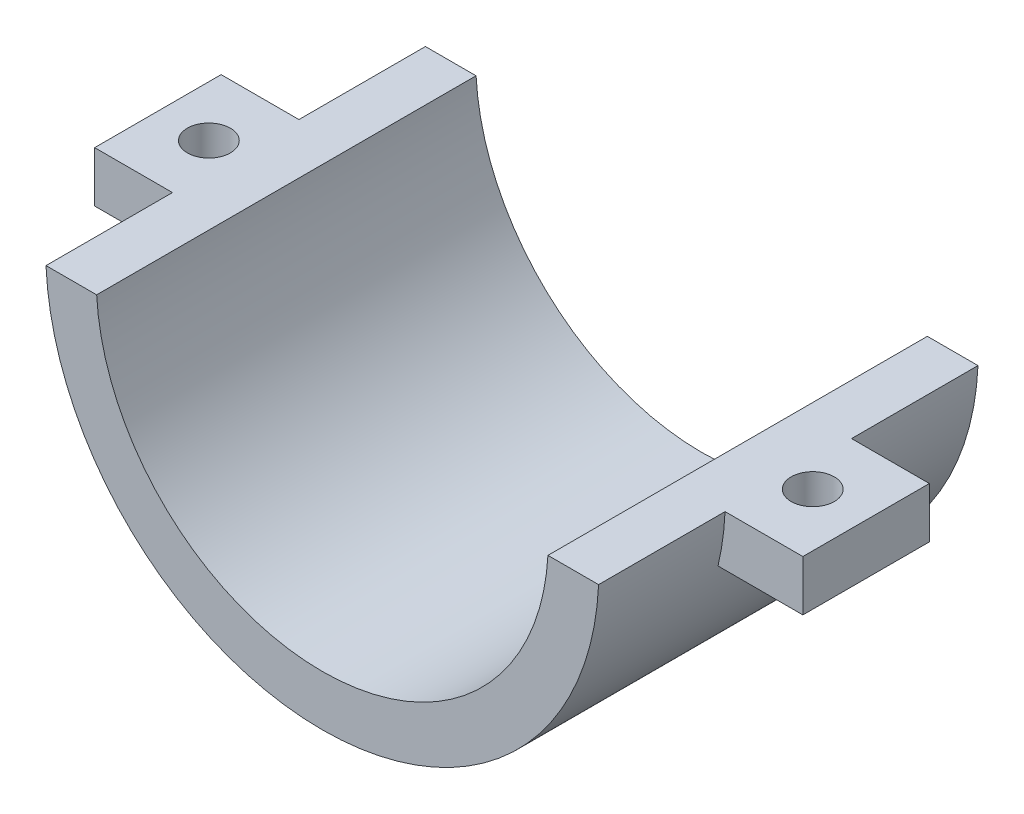
SolidWorks part; units mm, degrees
ref_plane "Front Plane" through (0, 0, 0) normal (0, 0, 1) x (1, 0, 0)
ref_plane "Top Plane" through (0, 0, 0) normal (0, 1, 0) x (1, 0, 0)
ref_plane "Right Plane" through (0, 0, 0) normal (1, 0, 0) x (0, 0, -1)
sketch "Sketch1" plane through (0, 0, 0) normal (0, 1, 0) x (1, 0, 0)
  line L0 (0, 19.621) -> (0, -19.621) construction
  line L2 (-21.87, 15) -> (-17.87, 15)
  line L3 (-21.87, 15) -> (-21.87, -15)
  line L4 (-21.87, -15) -> (-17.87, -15)
  line L5 (-17.87, 15) -> (-17.87, -15)
  line L6 (-21.87, 15) -> (-17.87, -15) construction
  line L7 (-21.87, -15) -> (-17.87, 15) construction
  point P0 (-19.87, 0)
  point P4 (0, 0)
  point P10 (-17.87, 0)
  dimension "D1" = 4
  dimension "D2" = 17.87
  dimension "D3" = 30
revolve "Revolve1" add sketch "Sketch1" angle 180 about L0
sketch "Sketch6" plane through (0, 0, 0) normal (0, 0, 1) x (1, 0, 0)
  line L0 (0, 0) -> (0, -14.1666) construction
  line L1 (-21.87, 0) -> (-17.87, 0) construction
  line L2 (-19.87, 0) -> (-28, 0)
  line L3 (-19.87, 0) -> (-19.87, -5)
  line L4 (-19.87, -5) -> (-28, -5)
  line L5 (-28, 0) -> (-28, -5)
  line L6 (19.87, -5) -> (28, -5)
  line L7 (28, 0) -> (28, -5)
  line L8 (19.87, 0) -> (28, 0)
  line L9 (19.87, 0) -> (19.87, -5)
  dimension "D1" = 8.13
  dimension "D2" = 5
extrude "Boss-Extrude3" add sketch "Sketch6" along normal blind 5 and the other way blind 5
hole_wizard "M3 Clearance Hole1" positions "Sketch7" profile "Sketch8" hole size "M3" standard "ISO"
sketch "Sketch7" plane through (0, 0, 0) normal (0, 1, 0) x (1, 0, 0)
  point P0 (-23.97, 0)
  point P3 (23.7783, 0)
sketch "Sketch8" plane through (-23.97, 0, 0) normal (1, 0, 0) x (0, 0, 1)
  line L0 (0, 0) -> (0, 9.8915)
  line L1 (0, 9.8915) -> (1.7, 8.87)
  line L2 (1.7, 8.87) -> (1.7, 0)
  line L5 (1.7, 0) -> (0, 0)
  line L10 (0, 9.8915) -> (-1.7, 8.87) construction
  line L11 (0, -6.35) -> (0, 107.95) construction
  dimension "Hole Dia." = 3.4
  dimension "Hole Depth" = 8.87
  dimension "Drill Angle" = 118
sketch "Sketch11" plane through (0, 0, 0) normal (0, 1, 0) x (1, 0, 0)
  line L1 (-31.0425, 20.9366) -> (31.0425, 20.9366)
  line L2 (-31.0425, 20.9366) -> (-31.0425, -20.9366)
  line L3 (-31.0425, -20.9366) -> (31.0425, -20.9366)
  line L4 (31.0425, 20.9366) -> (31.0425, -20.9366)
  line L5 (0, -20.9366) -> (0, 20.9366) construction
  line L6 (-31.0425, 0) -> (31.0425, 0) construction
  point P0 (0, 0)
extrude "Cut-Extrude1" cut sketch "Sketch11" against normal blind 1
